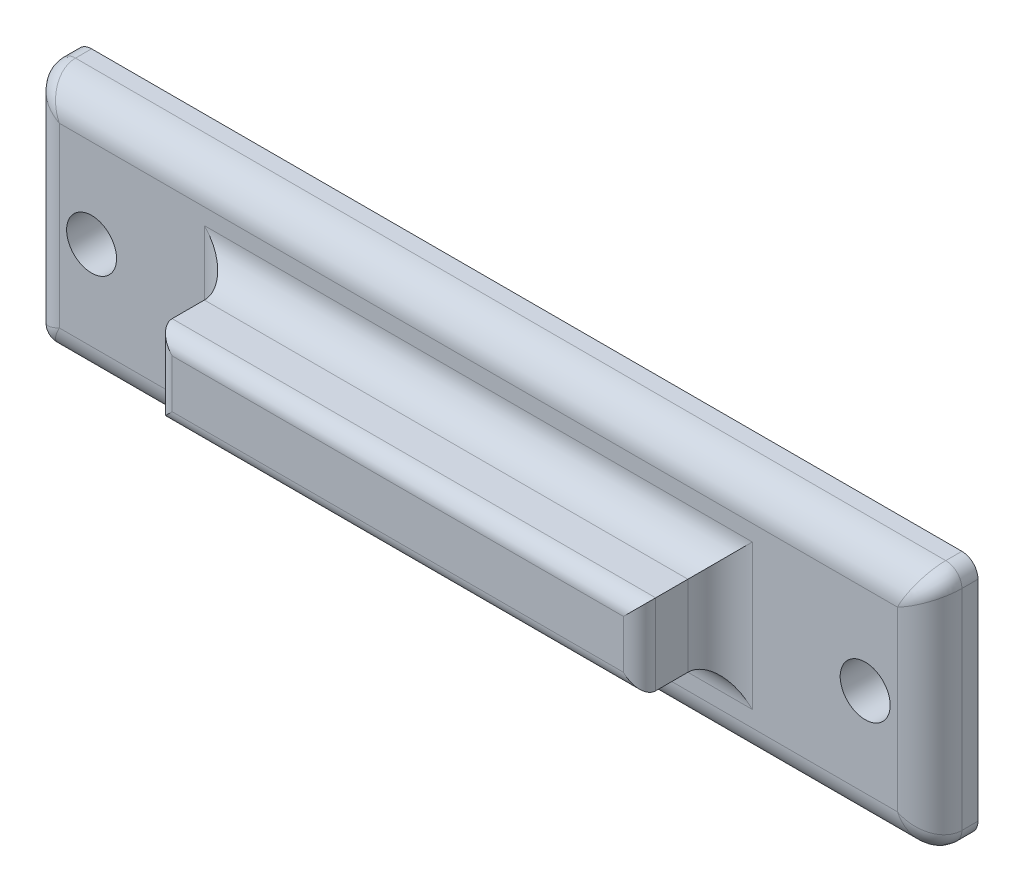
SolidWorks part; units mm, degrees
ref_plane "Front Plane" through (0, 0, 0) normal (0, 0, 1) x (1, 0, 0)
ref_plane "Top Plane" through (0, 0, 0) normal (0, 1, 0) x (1, 0, 0)
ref_plane "Right Plane" through (0, 0, 0) normal (1, 0, 0) x (0, 0, -1)
sketch "Sketch1" plane through (0, 0, 0) normal (0, 0, 1) x (1, 0, 0)
  line L0 (-31.4046, 0) -> (31.4046, 0) construction
  line L1 (-27, 7.5) -> (27, 7.5)
  line L2 (-28, 6.5) -> (-28, -6.5)
  line L3 (-27, -7.5) -> (27, -7.5)
  line L4 (28, 6.5) -> (28, -6.5)
  line L5 (-28, 7.5) -> (28, -7.5) construction
  line L6 (-28, -7.5) -> (28, 7.5) construction
  line L7 (0, 9.4204) -> (0, -9.4204) construction
  circle A0 centre (-24, 0) radius 1.55
  circle A1 centre (24, 0) radius 1.55
  arc A2 (27, -7.5) -> (28, -6.5) centre (27, -6.5) ccw
  arc A3 (28, 6.5) -> (27, 7.5) centre (27, 6.5) ccw
  arc A4 (-28, -6.5) -> (-27, -7.5) centre (-27, -6.5) ccw
  arc A5 (-28, 6.5) -> (-27, 7.5) centre (-27, 6.5) cw
  point P0 (0, 0)
  point P10 (0, 0)
  point P11 (0, 0)
  dimension "D3" = 24
  dimension "D4" = 3.1
  dimension "D5" = 1
  dimension "D1" = 56
  dimension "D2" = 15
extrude "Boss-Extrude1" add sketch "Sketch1" along normal blind 3
sketch "Sketch2" plane through (0, 0, 3) normal (0, 0, 1) x (1, 0, 0)
  line L7 (-15, 2.5) -> (15, 2.5)
  line L8 (-15, 2.5) -> (-15, -2.5)
  line L9 (-15, -2.5) -> (15, -2.5)
  line L10 (15, 2.5) -> (15, -2.5)
  line L11 (-15, 2.5) -> (15, -2.5) construction
  line L12 (-15, -2.5) -> (15, 2.5) construction
  point P11 (0, 0)
  dimension "D1" = 30
  dimension "D2" = 5
extrude "Boss-Extrude2" add sketch "Sketch2" along normal blind 5
fillet "Fillet2" radius 1 4 edges at (0, -2.5, 8) (-15, 0, 8) (0, 2.5, 8) (15, 0, 8)
fillet "Fillet3" radius 2 12 edges at (-15, 0, 3) (0, 2.5, 3) (15, 0, 3) (0, -2.5, 3) (27.7071, -7.2071, 3) (28, 0, 3) (27.7071, 7.2071, 3) (0, -7.5, 3) (-27.7071, -7.2071, 3) (-28, 0, 3) (-27.7071, 7.2071, 3) (0, 7.5, 3)
